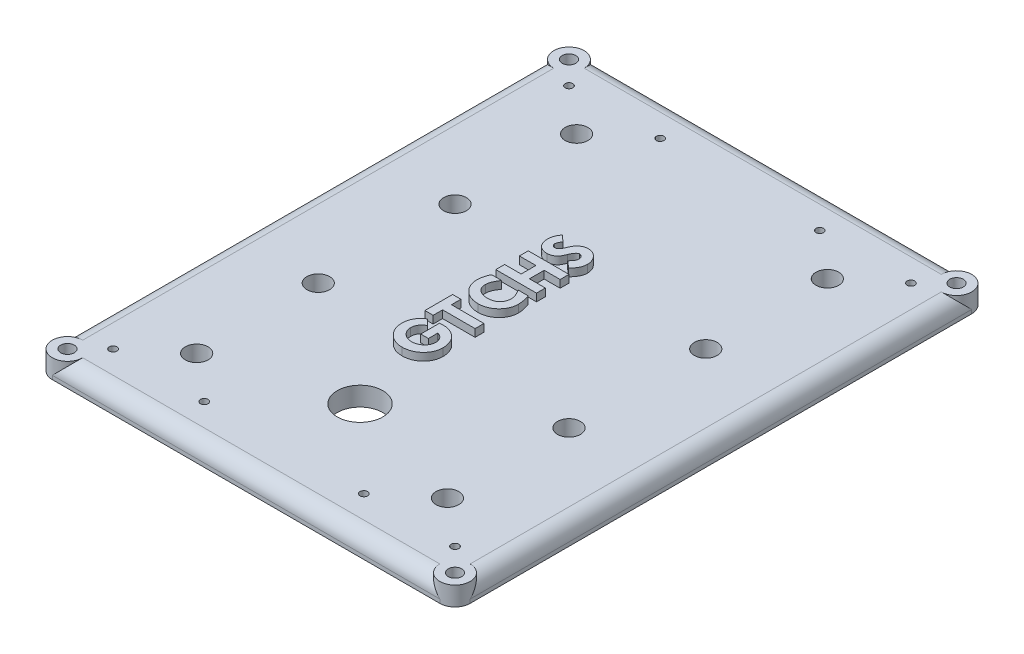
SolidWorks part; units mm, degrees
ref_plane "Front Plane" through (0, 0, 0) normal (0, 0, 1) x (1, 0, 0)
ref_plane "Top Plane" through (0, 0, 0) normal (0, 1, 0) x (1, 0, 0)
ref_plane "Right Plane" through (0, 0, 0) normal (1, 0, 0) x (0, 0, -1)
sketch "Sketch1" plane through (0, 0, 0) normal (0, 1, 0) x (1, 0, 0)
  line L1 (0, 0) -> (69.85, 0)
  line L2 (0, 0) -> (0, -88.9)
  line L3 (0, -88.9) -> (69.85, -88.9)
  line L4 (69.85, 0) -> (69.85, -88.9)
  dimension "D1" = 88.9
  dimension "D2" = 69.85
extrude "Boss-Extrude1" add sketch "Sketch1" along normal blind 3.175
sketch "Sketch2" plane through (0, 3.175, 0) normal (0, 1, 0) x (1, 0, 0)
  line L0 (0, -88.9) -> (69.85, -88.9) construction
  line L1 (0, 0) -> (0, -88.9) construction
  line L2 (69.85, 0) -> (0, 0) construction
  circle A0 centre (13.97, -12.7) radius 1.905
  circle A1 centre (13.97, -33.02) radius 1.905
  circle A2 centre (13.97, -55.88) radius 1.905
  circle A3 centre (13.97, -76.2) radius 1.905
  circle A4 centre (34.925, -69.85) radius 3.81
  circle A5 centre (55.88, -76.2) radius 1.905
  circle A6 centre (55.88, -55.88) radius 1.905
  circle A7 centre (55.88, -33.02) radius 1.905
  circle A8 centre (55.88, -12.7) radius 1.905
  circle A9 centre (6.35, -82.55) radius 0.635
  circle A10 centre (21.59, -82.55) radius 0.635
  circle A11 centre (6.35, -6.35) radius 0.635
  circle A12 centre (21.59, -6.35) radius 0.635
  circle A13 centre (48.26, -82.55) radius 0.635
  circle A14 centre (63.5, -82.55) radius 0.635
  circle A15 centre (48.26, -6.35) radius 0.635
  circle A16 centre (63.5, -6.35) radius 0.635
  point P49 (34.925, -88.9)
  dimension "D1" = 3.81
  dimension "D2" = 1.27
  dimension "D12" = 7.62
  dimension "D3" = 7.62
  dimension "D4" = 7.62
  dimension "D5" = 7.62
  dimension "D6" = 7.62
  dimension "D7" = 20.32
  dimension "D8" = 20.32
  dimension "D9" = 22.86
  dimension "D10" = 6.35
  dimension "D11" = 6.35
  dimension "D13" = 19.05
  dimension "D14" = 41.91
  dimension "D15" = 6.35
  dimension "D16" = 6.35
extrude "Cut-Extrude1" cut sketch "Sketch2" against normal through all
fillet "Fillet1" radius 2.54 8 edges at (0, 1.5875, 88.9) (69.85, 1.5875, 88.9) (69.85, 1.5875, 0) (0, 1.5875, 0) (34.925, 3.175, 0) (69.85, 3.175, 44.45) (34.925, 3.175, 88.9) (0, 3.175, 44.45)
sketch "Sketch3" plane through (0, 3.175, 0) normal (0, 1, 0) x (1, 0, 0)
  circle A0 centre (2.54, -86.36) radius 2.54
  circle A1 centre (2.54, -2.54) radius 2.54
  circle A2 centre (67.31, -2.54) radius 2.54
  circle A3 centre (67.31, -86.36) radius 2.54
  dimension "D1" = 5.08
extrude "Cut-Extrude2" cut sketch "Sketch3" against normal blind 2.54
extrude "Boss-Extrude2" add sketch "Sketch3<2>" against normal blind 2.54
sketch "Sketch3<2>" plane through (0, 3.175, 0) normal (0, 1, 0) x (1, 0, 0) same geometry as "Sketch3"
hole_wizard "#4-40 Tapped Hole1" positions "Sketch4" profile "Sketch5" tap size "#4-40" standard "ANSI Inch" end condition through all
sketch "Sketch4" plane through (0, 3.175, 0) normal (0, 1, 0) x (1, 0, 0)
  point P0 (2.54, -2.54)
  point P3 (67.31, -2.54)
  point P6 (67.31, -86.36)
  point P9 (2.54, -86.36)
sketch "Sketch5" plane through (2.54, 3.175, 2.54) normal (1, 0, 0) x (0, 0, 1)
  line L0 (0, 0) -> (0, 3.175)
  line L1 (0, 3.175) -> (1.1303, 3.175)
  line L2 (1.1303, 3.175) -> (1.1303, 0)
  line L5 (1.1303, 0) -> (0, 0)
  line L11 (0, -6.35) -> (0, 107.95) construction
  dimension "Thru Tap Drill Dia." = 2.2606
  dimension "Thru Tap Drill Depth" = 3.175
cosmetic thread "Hole Thread1" parameters "D2"=2.8448
cosmetic thread "Hole Thread2" parameters "D2"=2.8448
cosmetic thread "Hole Thread3" parameters "D2"=2.8448
cosmetic thread "Hole Thread4" parameters "D2"=2.8448
sketch "Sketch6" plane through (0, 3.175, 0) normal (0, 1, 0) x (1, 0, 0)
  line L0 (34.925, -2.54) -> (34.925, -86.36) construction
  line L1 (64.77, -2.54) -> (5.08, -2.54) construction
  line L2 (5.08, -86.36) -> (64.77, -86.36) construction
  text T0 "GTCHS" font "Tw Cen MT" height in points 26
  point P4 (34.925, -2.54)
  point P5 (34.925, -109.7058)
  point P6 (34.925, 25.2688)
  point P8 (34.925, -2.54)
  point P9 (34.925, -86.36)
extrude "Boss-Extrude3" add sketch "Sketch6" along normal blind 1.27
